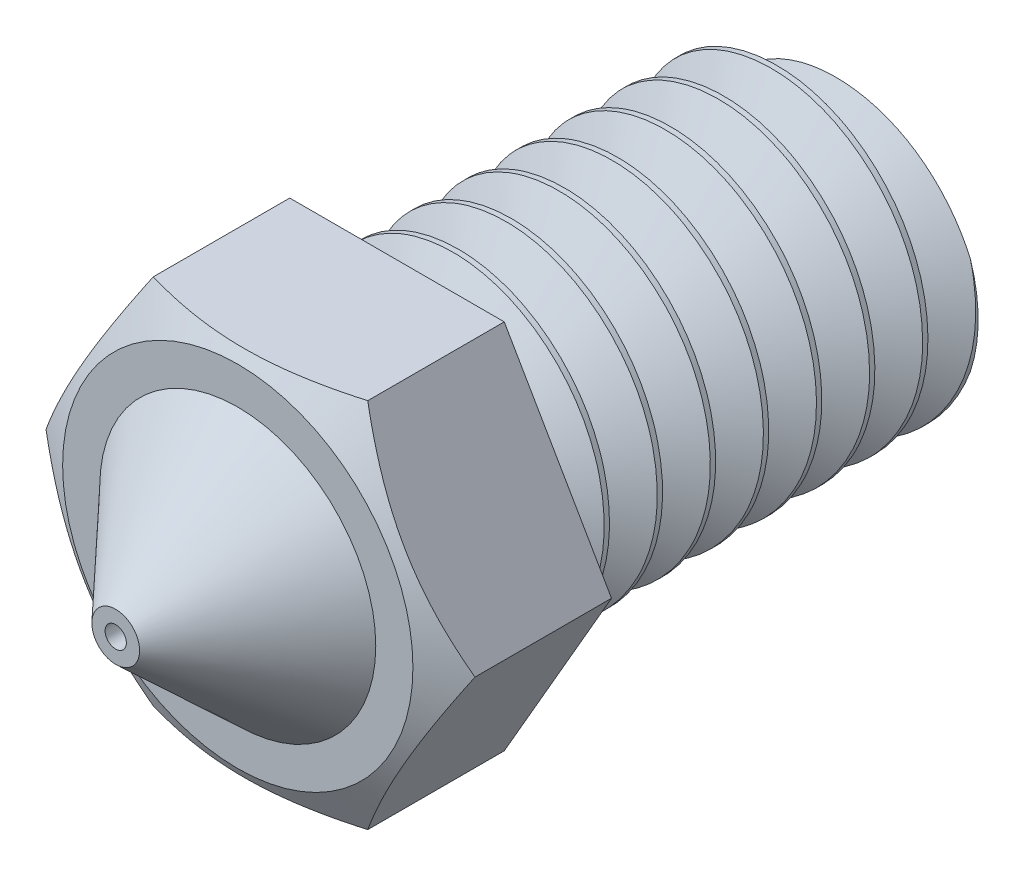
SolidWorks part; units mm, degrees
ref_plane "Front Plane" through (0, 0, 0) normal (0, 0, 1) x (1, 0, 0)
ref_plane "Top Plane" through (0, 0, 0) normal (0, 1, 0) x (1, 0, 0)
ref_plane "Right Plane" through (0, 0, 0) normal (1, 0, 0) x (0, 0, -1)
sketch "Sketch1" plane through (0, 0, 0) normal (0, 0, 1) x (1, 0, 0)
  circle A0 centre (0, 0) radius 2.95
  circle A1 centre (0, 0) radius 0.875
  dimension "D1" = 5.9
  dimension "D2" = 1.75
extrude "Boss-Extrude1" add sketch "Sketch1" along normal blind 8
sketch "Sketch2" plane through (0, 0, 8) normal (0, 0, 1) x (1, 0, 0)
  line L1 (4.0415, 0) -> (2.0207, 3.5)
  line L2 (2.0207, 3.5) -> (-2.0207, 3.5)
  line L3 (-2.0207, 3.5) -> (-4.0415, 0)
  line L4 (-4.0415, 0) -> (-2.0207, -3.5)
  line L5 (-2.0207, -3.5) -> (2.0207, -3.5)
  line L6 (2.0207, -3.5) -> (4.0415, 0)
  circle A0 centre (0, 0) radius 3.5 construction
  circle A1 centre (0, 0) radius 0.875
  dimension "D2" = 1.75
  dimension "D1" = 7
extrude "Boss-Extrude2" add sketch "Sketch2" along normal blind 3
sketch "Sketch3" plane through (0, 0, 11) normal (0, 0, 1) x (1, 0, 0)
  circle A0 centre (0, 0) radius 2.6
  dimension "D1" = 5.2
extrude "Boss-Extrude3" add sketch "Sketch3" along normal blind 2.3
chamfer "Chamfer1" distance 2.3 distance2 2.15 1 edges at (2.6, 0, 13.3) first distance on face at (2.6, 0, 13.3)
sketch "Sketch4" plane through (0, 0, 13.3) normal (0, 0, 1) x (1, 0, 0)
  circle A0 centre (0, 0) radius 0.2
  dimension "D1" = 0.4
extrude "Cut-Extrude1" cut sketch "Sketch4" against normal blind 17.3
ref_plane "Plane1" through (0, 0, -5) normal (0, 0, -1) x (-1, 0, 0)
sketch "Sketch9" plane through (0, 0, 0) normal (1, 0, 0) x (0, 0, -1)
  line L0 (-17.2792, 0) -> (2.0525, 0) construction
  line L1 (-11, 3.3) -> (-10.4226, 4.3)
  line L2 (-10.4226, 4.3) -> (-11, 4.3)
  line L3 (-11, 4.3) -> (-11, 3.3)
  line L4 (-11, 0) -> (-11, 3.5) construction
  dimension "D1" = 30
  dimension "D2" = 3.3
  dimension "D3" = 1
revolve "Cut-Revolve1" cut sketch "Sketch9" angle 360 about L0
sketch "Sketch5" plane through (0, 0, -5) normal (0, 0, -1) x (-1, 0, 0)
  circle A0 centre (0, 0) radius 2.95
  dimension "D1" = 5.9
curve "Helix/Spiral1" pitch 1 height 13 radius 2.95 left hand yes centre (0, 0, -5) axis (0, 0, 1) start towards (-1, 0, 0)
sketch "Sketch10" plane through (0, 0, 0) normal (0, 1, 0) x (1, 0, 0)
  line L0 (-2.95, 5.45) -> (-2.95, 4.55)
  line L1 (-2.95, 4.55) -> (-2.1706, 5)
  line L2 (-2.1706, 5) -> (-2.95, 5.45)
  line L3 (-2.1706, 5) -> (-2.95, 5) construction
  spline S0 degree 3 poles (-2.95, 5) (-2.95, 4.9792) (-2.7949, 4.9371) (-2.1327, 4.8744) (-1.1427, 4.8116) (0.023, 4.7488) (1.1851, 4.686) (2.165, 4.6232) (2.8122, 4.5604) (3.0272, 4.4976) (2.7769, 4.4348) (2.0998, 4.372) (1.1, 4.3092) (-0.0689, 4.2464) (-1.2272, 4.1836) (-2.1969, 4.1208) (-2.8289, 4.058) (-3.0262, 3.9952) (-2.7583, 3.9324) (-2.0665, 3.8696) (-1.057, 3.8068) (0.1148, 3.744) (1.2691, 3.6812) (2.2283, 3.6184) (2.845, 3.5556) (3.0244, 3.4928) (2.739, 3.43) (2.0326, 3.3671) (1.0139, 3.3043) (-0.1607, 3.2415) (-1.3106, 3.1787) (-2.2591, 3.1159) (-2.8604, 3.0531) (-3.022, 2.9903) (-2.7191, 2.9275) (-1.9984, 2.8647) (-0.9705, 2.8019) (0.2066, 2.7391) (1.3519, 2.6763) (2.2894, 2.6135) (2.8751, 2.5507) (3.0188, 2.4879) (2.6986, 2.4251) (1.9636, 2.3623) (0.9268, 2.2995) (-0.2524, 2.2367) (-1.3929, 2.1739) (-2.3192, 2.1111) (-2.8892, 2.0483) (-3.015, 1.9855) (-2.6775, 1.9227) (-1.9284, 1.8599) (-0.883, 1.7971) (0.2982, 1.7343) (1.4335, 1.6715) (2.3485, 1.6087) (2.9026, 1.5459) (3.0105, 1.4831) (2.6557, 1.4203) (1.8928, 1.3575) (0.8389, 1.2947) (-0.3439, 1.2319) (-1.4738, 1.1691) (-2.3772, 1.1063) (-2.9153, 1.0435) (-3.0053, 0.9807) (-2.6334, 0.9179) (-1.8567, 0.8551) (-0.7947, 0.7923) (0.3895, 0.7295) (1.5138, 0.6667) (2.4054, 0.6039) (2.9273, 0.5411) (2.9994, 0.4783) (2.6104, 0.4155) (1.8202, 0.3527) (0.7503, 0.2899) (-0.435, 0.2271) (-1.5534, 0.1643) (-2.433, 0.1014) (-2.9387, 0.0386) (-2.9928, -0.0242) (-2.5868, -0.087) (-1.7833, -0.1498) (-0.7057, -0.2126) (0.4804, -0.2754) (1.5927, -0.3382) (2.4601, -0.401) (2.9494, -0.4638) (2.9855, -0.5266) (2.5626, -0.5894) (1.7459, -0.6522) (0.6609, -0.715) (-0.5257, -0.7778) (-1.6315, -0.8406) (-2.4866, -0.9034) (-2.9595, -0.9662) (-2.9775, -1.029) (-2.5379, -1.0918) (-1.7082, -1.1546) (-0.616, -1.2174) (0.5709, -1.2802) (1.6701, -1.343) (2.5125, -1.4058) (2.9688, -1.4686) (2.9688, -1.5314) (2.5125, -1.5942) (1.6701, -1.657) (0.5709, -1.7198) (-0.616, -1.7826) (-1.7082, -1.8454) (-2.5379, -1.9082) (-2.9775, -1.971) (-2.9595, -2.0338) (-2.4866, -2.0966) (-1.6315, -2.1594) (-0.5257, -2.2222) (0.6609, -2.285) (1.7459, -2.3478) (2.5626, -2.4106) (2.9855, -2.4734) (2.9494, -2.5362) (2.4601, -2.599) (1.5927, -2.6618) (0.4804, -2.7246) (-0.7057, -2.7874) (-1.7833, -2.8502) (-2.5868, -2.913) (-2.9928, -2.9758) (-2.9387, -3.0386) (-2.433, -3.1014) (-1.5534, -3.1643) (-0.435, -3.2271) (0.7503, -3.2899) (1.8202, -3.3527) (2.6104, -3.4155) (2.9994, -3.4783) (2.9273, -3.5411) (2.4054, -3.6039) (1.5138, -3.6667) (0.3895, -3.7295) (-0.7947, -3.7923) (-1.8567, -3.8551) (-2.6334, -3.9179) (-3.0053, -3.9807) (-2.9153, -4.0435) (-2.3772, -4.1063) (-1.4738, -4.1691) (-0.3439, -4.2319) (0.8389, -4.2947) (1.8928, -4.3575) (2.6557, -4.4203) (3.0105, -4.4831) (2.9026, -4.5459) (2.3485, -4.6087) (1.4335, -4.6715) (0.2982, -4.7343) (-0.883, -4.7971) (-1.9284, -4.8599) (-2.6775, -4.9227) (-3.015, -4.9855) (-2.8892, -5.0483) (-2.3192, -5.1111) (-1.3929, -5.1739) (-0.2524, -5.2367) (0.9268, -5.2995) (1.9636, -5.3623) (2.6986, -5.4251) (3.0188, -5.4879) (2.8751, -5.5507) (2.2894, -5.6135) (1.3519, -5.6763) (0.2066, -5.7391) (-0.9705, -5.8019) (-1.9984, -5.8647) (-2.7191, -5.9275) (-3.022, -5.9903) (-2.8604, -6.0531) (-2.2591, -6.1159) (-1.3106, -6.1787) (-0.1607, -6.2415) (1.0139, -6.3043) (2.0326, -6.3671) (2.739, -6.43) (3.0244, -6.4928) (2.845, -6.5556) (2.2283, -6.6184) (1.2691, -6.6812) (0.1148, -6.744) (-1.057, -6.8068) (-2.0665, -6.8696) (-2.7583, -6.9324) (-3.0262, -6.9952) (-2.8289, -7.058) (-2.1969, -7.1208) (-1.2272, -7.1836) (-0.0689, -7.2464) (1.1, -7.3092) (2.0998, -7.372) (2.7769, -7.4348) (3.0272, -7.4976) (2.8122, -7.5604) (2.165, -7.6232) (1.1851, -7.686) (0.023, -7.7488) (-1.1427, -7.8116) (-2.1327, -7.8744) (-2.7949, -7.9371) (-2.95, -7.9792) (-2.95, -8) knots 0 0 0 0 0.004831 0.009662 0.014493 0.019324 0.024155 0.028986 0.033816 0.038647 0.043478 0.048309 0.05314 0.057971 0.062802 0.067633 0.072464 0.077295 0.082126 0.086957 0.091787 0.096618 0.101449 0.10628 0.111111 0.115942 0.120773 0.125604 0.130435 0.135266 0.140097 0.144928 0.149758 0.154589 0.15942 0.164251 0.169082 0.173913 0.178744 0.183575 0.188406 0.193237 0.198068 0.202899 0.207729 0.21256 0.217391 0.222222 0.227053 0.231884 0.236715 0.241546 0.246377 0.251208 0.256039 0.26087 0.2657 0.270531 0.275362 0.280193 0.285024 0.289855 0.294686 0.299517 0.304348 0.309179 0.31401 0.318841 0.323671 0.328502 0.333333 0.338164 0.342995 0.347826 0.352657 0.357488 0.362319 0.36715 0.371981 0.376812 0.381643 0.386473 0.391304 0.396135 0.400966 0.405797 0.410628 0.415459 0.42029 0.425121 0.429952 0.434783 0.439614 0.444444 0.449275 0.454106 0.458937 0.463768 0.468599 0.47343 0.478261 0.483092 0.487923 0.492754 0.497585 0.502415 0.507246 0.512077 0.516908 0.521739 0.52657 0.531401 0.536232 0.541063 0.545894 0.550725 0.555556 0.560386 0.565217 0.570048 0.574879 0.57971 0.584541 0.589372 0.594203 0.599034 0.603865 0.608696 0.613527 0.618357 0.623188 0.628019 0.63285 0.637681 0.642512 0.647343 0.652174 0.657005 0.661836 0.666667 0.671498 0.676329 0.681159 0.68599 0.690821 0.695652 0.700483 0.705314 0.710145 0.714976 0.719807 0.724638 0.729469 0.7343 0.73913 0.743961 0.748792 0.753623 0.758454 0.763285 0.768116 0.772947 0.777778 0.782609 0.78744 0.792271 0.797101 0.801932 0.806763 0.811594 0.816425 0.821256 0.826087 0.830918 0.835749 0.84058 0.845411 0.850242 0.855072 0.859903 0.864734 0.869565 0.874396 0.879227 0.884058 0.888889 0.89372 0.898551 0.903382 0.908213 0.913043 0.917874 0.922705 0.927536 0.932367 0.937198 0.942029 0.94686 0.951691 0.956522 0.961353 0.966184 0.971014 0.975845 0.980676 0.985507 0.990338 0.995169 1 1 1 1 construction
  point P6 (0, 0)
  dimension "D1" = 0.9
  dimension "D2" = 60
sweep "Cut-Sweep1" cut profiles "Sketch10" path "Helix/Spiral1" align with end faces yes
